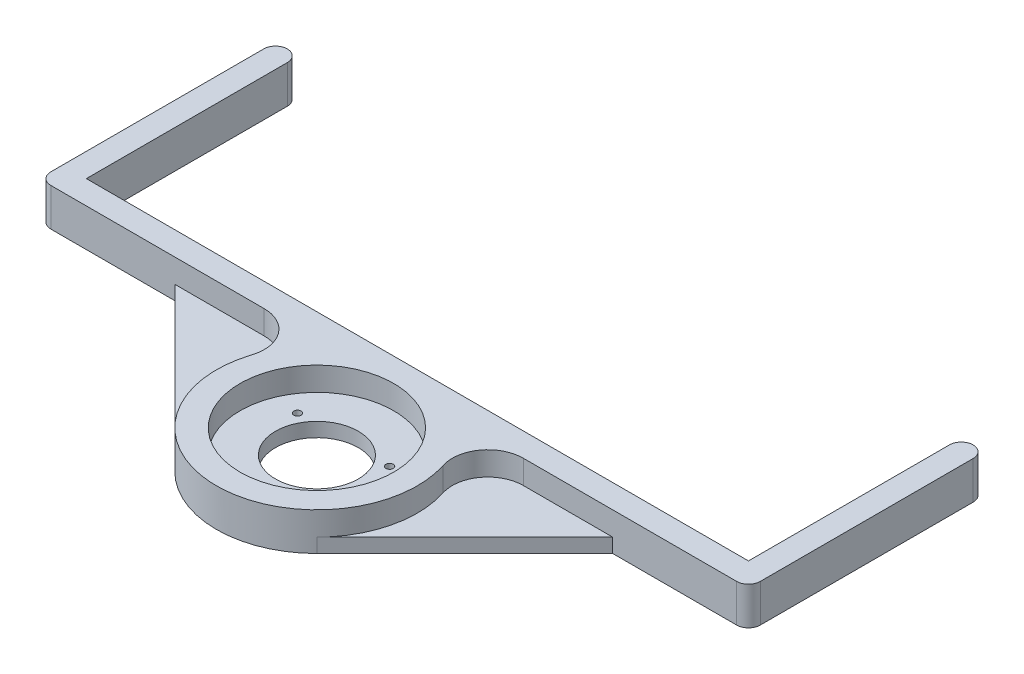
SolidWorks part; units mm, degrees
material "PET"
ref_plane "Front Plane" through (0, 0, 0) normal (0, 0, 1) x (1, 0, 0)
ref_plane "Top Plane" through (0, 0, 0) normal (0, 1, 0) x (1, 0, 0)
ref_plane "Right Plane" through (0, 0, 0) normal (1, 0, 0) x (0, 0, -1)
sketch "Sketch1" plane through (0, 0, 0) normal (0, 1, 0) x (1, 0, 0)
  line L0 (0, 42.5) -> (140, 42.5)
  line L9 (150, 42.5) -> (150, 32.5)
  line L10 (150, 32.5) -> (27.3861, 32.5)
  line L11 (-150, 32.5) -> (-150, 42.5)
  line L12 (-140, 42.5) -> (0, 42.5)
  line L13 (-27.3861, 32.5) -> (-150, 32.5)
  line L14 (150, 42.5) -> (150, 132.5)
  line L15 (150, 132.5) -> (140, 132.5)
  line L16 (140, 47.5) -> (140, 317.5) construction
  line L17 (140, 132.5) -> (140, 42.5)
  line L18 (-150, 42.5) -> (-150, 132.5)
  line L19 (-150, 132.5) -> (-140, 132.5)
  line L20 (-140, 47.5) -> (-140, 317.5) construction
  line L21 (-140, 132.5) -> (-140, 42.5)
  circle A2 centre (0, 0) radius 32.5
  arc A3 (-27.3861, 32.5) -> (27.3861, 32.5) centre (0, 0) ccw
  dimension "D5" = 10
  dimension "D1" = 65
  dimension "D2" = 85
  dimension "D3" = 300
  dimension "D4" = 100
extrude "Boss-Extrude1" add sketch "Sketch1" along normal blind 10
fillet "Fillet1" radius 5 6 edges at (150, 5, -132.5) (140, 5, -132.5) (150, 5, -32.5) (-150, 5, -32.5) (-140, 5, -132.5) (-150, 5, -132.5)
fillet "Fillet2" radius 15 2 edges at (27.3861, 5, -32.5) (-27.3861, 5, -32.5)
sketch "Sketch2" plane through (0, 0, 0) normal (0, -1, 0) x (1, 0, 0)
  line L0 (-30.052, 30.052) -> (-92.6041, -32.5)
  line L1 (-145, -32.5) -> (-54.7723, -32.5) construction
  line L2 (30.052, 30.052) -> (92.6041, -32.5)
  line L7 (150, -127.5) -> (150, -37.5)
  line L8 (145, -32.5) -> (54.7723, -32.5)
  line L9 (-54.7723, -32.5) -> (-145, -32.5)
  line L10 (-150, -37.5) -> (-150, -127.5)
  line L11 (-140, -127.5) -> (-140, -42.5)
  line L12 (-140, -42.5) -> (140, -42.5)
  line L13 (140, -42.5) -> (140, -127.5)
  line L14 (150, -127.5) -> (150, -37.5)
  line L15 (145, -32.5) -> (92.6041, -32.5)
  line L16 (-92.6041, -32.5) -> (-145, -32.5)
  line L17 (-150, -37.5) -> (-150, -127.5)
  line L18 (-140, -127.5) -> (-140, -42.5)
  line L19 (-140, -42.5) -> (140, -42.5)
  line L20 (140, -42.5) -> (140, -127.5)
  circle A7 centre (0, 0) radius 22.5 construction
  circle A8 centre (0, 22.5) radius 1.55
  arc A9 (140, -127.5) -> (145, -132.5) centre (145, -127.5) ccw
  arc A10 (145, -132.5) -> (150, -127.5) centre (145, -127.5) ccw
  arc A11 (150, -37.5) -> (145, -32.5) centre (145, -37.5) ccw
  arc A12 (40.4838, -12.9348) -> (54.7723, -32.5) centre (54.7723, -17.5) ccw
  arc A13 (40.4838, -12.9348) -> (-40.4838, -12.9348) centre (0, 0) ccw
  arc A14 (-54.7723, -32.5) -> (-40.4838, -12.9348) centre (-54.7723, -17.5) ccw
  arc A15 (-145, -32.5) -> (-150, -37.5) centre (-145, -37.5) ccw
  arc A16 (-150, -127.5) -> (-145, -132.5) centre (-145, -127.5) ccw
  arc A17 (-145, -132.5) -> (-140, -127.5) centre (-145, -127.5) ccw
  arc A18 (140, -127.5) -> (145, -132.5) centre (145, -127.5) ccw
  arc A19 (145, -132.5) -> (150, -127.5) centre (145, -127.5) ccw
  arc A20 (150, -37.5) -> (145, -32.5) centre (145, -37.5) ccw
  arc A22 (30.052, 30.052) -> (-30.052, 30.052) centre (0, 0) ccw
  arc A24 (-145, -32.5) -> (-150, -37.5) centre (-145, -37.5) ccw
  arc A25 (-150, -127.5) -> (-145, -132.5) centre (-145, -127.5) ccw
  arc A26 (-145, -132.5) -> (-140, -127.5) centre (-145, -127.5) ccw
  circle A27 centre (19.4856, -11.25) radius 1.55
  circle A28 centre (-19.4856, -11.25) radius 1.55
  circle A29 centre (0, 0) radius 17.5
  point P49 (0, 0)
  dimension "D6" = 45
  dimension "D7" = 3.1
  dimension "D9" = 35
  dimension "D2" = 45
  dimension "D1" = 0
  dimension "D8" = 3
extrude "Boss-Extrude2" add sketch "Sketch2" along normal blind 6
sketch "Sketch4" plane through (0, -6, 0) normal (0, -1, 0) x (1, 0, 0)
  line L0 (17.5196, -14.6552) -> (21.4515, -14.6552)
  line L1 (3.9319, 22.5) -> (1.966, 25.9052)
  line L2 (1.966, 25.9052) -> (-1.966, 25.9052)
  line L3 (-1.966, 25.9052) -> (-3.9319, 22.5)
  line L4 (-3.9319, 22.5) -> (-1.966, 19.0948)
  line L5 (-1.966, 19.0948) -> (1.966, 19.0948)
  line L6 (1.966, 19.0948) -> (3.9319, 22.5)
  line L7 (21.4515, -14.6552) -> (23.4175, -11.25)
  line L8 (23.4175, -11.25) -> (21.4515, -7.8448)
  line L9 (21.4515, -7.8448) -> (17.5196, -7.8448)
  line L10 (17.5196, -7.8448) -> (15.5536, -11.25)
  line L11 (15.5536, -11.25) -> (17.5196, -14.6552)
  line L12 (-21.4515, -7.8448) -> (-23.4175, -11.25)
  line L13 (-23.4175, -11.25) -> (-21.4515, -14.6552)
  line L14 (-21.4515, -14.6552) -> (-17.5196, -14.6552)
  line L15 (-17.5196, -14.6552) -> (-15.5536, -11.25)
  line L16 (-15.5536, -11.25) -> (-17.5196, -7.8448)
  line L17 (-17.5196, -7.8448) -> (-21.4515, -7.8448)
  circle A0 centre (0, 22.5) radius 3.4052 construction
  point P23 (0, 0)
  dimension "D1" = 3
extrude "Cut-Extrude1" cut sketch "Sketch4" against normal blind 3
